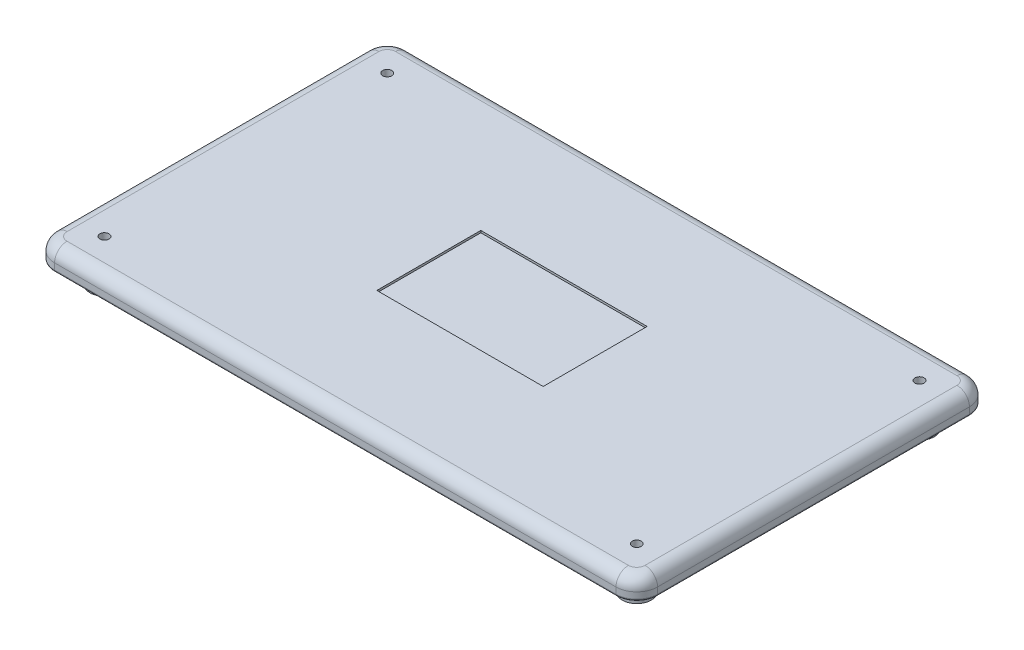
SolidWorks part; units mm, degrees
ref_plane "Front Plane" through (0, 0, 0) normal (0, 0, 1) x (1, 0, 0)
ref_plane "Top Plane" through (0, 0, 0) normal (0, 1, 0) x (1, 0, 0)
ref_plane "Right Plane" through (0, 0, 0) normal (1, 0, 0) x (0, 0, -1)
sketch "Sketch1" plane through (0, 0, 0) normal (0, 1, 0) x (1, 0, 0)
  line L1 (-72.5, 42.5) -> (72.5, 42.5)
  line L2 (-72.5, 42.5) -> (-72.5, -42.5)
  line L3 (-72.5, -42.5) -> (72.5, -42.5)
  line L4 (72.5, 42.5) -> (72.5, -42.5)
  line L5 (-72.5, 42.5) -> (72.5, -42.5) construction
  line L6 (-72.5, -42.5) -> (72.5, 42.5) construction
  point P0 (0, 0)
  dimension "D1" = 145
  dimension "D2" = 85
extrude "Boss-Extrude1" add sketch "Sketch1" along normal blind 5
fillet "Fillet1" radius 5 4 edges at (72.5, 2.5, -42.5) (-72.5, 2.5, -42.5) (72.5, 2.5, 42.5) (-72.5, 2.5, 42.5)
fillet "Fillet2" radius 3 8 edges at (71.0355, 5, 41.0355) (0, 5, 42.5) (-71.0355, 5, 41.0355) (-72.5, 5, 0) (-71.0355, 5, -41.0355) (0, 5, -42.5) (71.0355, 5, -41.0355) (72.5, 5, 0)
shell "Shell1" thickness 2 removed face at (0, 0, 0)
sketch "Sketch3" plane through (0, 3, 0) normal (0, -1, 0) x (1, 0, 0)
  line L0 (-60, -25) -> (-20, -25) construction
  line L1 (-60, 25) -> (60, 25) construction
  line L2 (-60, 25) -> (-60, -25) construction
  line L4 (60, 25) -> (60, -25) construction
  line L5 (-60, 25) -> (60, -25) construction
  line L6 (-60, -25) -> (60, 25) construction
  line L7 (-20, -25) -> (20, -25) construction
  line L8 (20, -25) -> (60, -25) construction
  line L9 (-20, -25) -> (-20, 25) construction
  line L10 (20, -25) -> (20, 25) construction
  circle A0 centre (-60, 25) radius 2.5
  circle A1 centre (-60, -25) radius 2.5
  circle A2 centre (60, -25) radius 2.5
  circle A3 centre (60, 25) radius 2.5
  circle A4 centre (-20, -25) radius 2.5
  circle A5 centre (20, -25) radius 2.5
  circle A6 centre (20, 25) radius 2.5
  circle A7 centre (-20, 25) radius 2.5
  point P0 (0, 0)
  dimension "D3" = 5
  dimension "D1" = 50
  dimension "D2" = 120
extrude "Boss-Extrude2" add sketch "Sketch3" along normal blind 5
sketch "Sketch2" plane through (0, 5, 0) normal (0, -1, 0) x (1, 0, 0)
  line L1 (-20, 12.5) -> (20, 12.5)
  line L2 (-20, 12.5) -> (-20, -12.5)
  line L3 (-20, -12.5) -> (20, -12.5)
  line L4 (20, 12.5) -> (20, -12.5)
  line L5 (-20, 12.5) -> (20, -12.5) construction
  line L6 (-20, -12.5) -> (20, 12.5) construction
  point P0 (0, 0)
  dimension "D1" = 25
  dimension "D2" = 40
extrude "Cut-Extrude1" cut sketch "Sketch2" along normal blind 0.5
sketch "Sketch4" plane through (0, -2, 0) normal (0, -1, 0) x (1, 0, 0)
  line L1 (-64, 34) -> (64, 34) construction
  line L2 (-64, 34) -> (-64, -34) construction
  line L3 (-64, -34) -> (64, -34) construction
  line L4 (64, 34) -> (64, -34) construction
  line L5 (-64, 34) -> (64, -34) construction
  line L6 (-64, -34) -> (64, 34) construction
  circle A1 centre (-64, 34) radius 3.5
  circle A2 centre (-64, -34) radius 3.5
  circle A3 centre (64, 34) radius 3.5
  circle A4 centre (64, -34) radius 3.5
  point P2 (0, 0)
  dimension "D1" = 7
  dimension "D2" = 128
  dimension "D3" = 68
extrude "Boss-Extrude3" add sketch "Sketch4" along normal blind 3 and the other way up to body separate body
hole_wizard "Ø2.2 (2.2) Diameter Hole1" positions "Sketch6" profile "Sketch7" hole size "Ø2.2" standard "ANSI Metric"
sketch "Sketch6" plane through (0, -2, 0) normal (0, -1, 0) x (-1, 0, 0)
  point P0 (-60, -25)
  point P3 (-60, 25)
  point P6 (-20, 25)
  point P9 (-20, -25)
  point P12 (20, -25)
  point P15 (20, 25)
  point P18 (60, 25)
  point P21 (60, -25)
sketch "Sketch7" plane through (60, -2, 25) normal (1, 0, 0) x (0, 0, -1)
  line L0 (0, 0) -> (0, 5)
  line L1 (0, 5) -> (1.1, 4.3391)
  line L2 (1.1, 4.3391) -> (1.1, 0)
  line L5 (1.1, 0) -> (0, 0)
  line L10 (0, 5) -> (-1.1, 4.3391) construction
  line L11 (0, -6.35) -> (0, 107.95) construction
  dimension "Hole Dia." = 2.2
  dimension "Hole Depth" = 5
  dimension "Drill Angle" = 118
hole_wizard "Ø2.2 (2.2) Diameter Hole2" positions "Sketch8" profile "Sketch9" hole size "Ø2.2" standard "ANSI Metric" end condition through all
sketch "Sketch8" plane through (0, -5, 0) normal (0, -1, 0) x (-1, 0, 0)
  point P0 (-64, -34)
  point P3 (-64, 34)
  point P6 (64, 34)
  point P9 (64, -34)
sketch "Sketch9" plane through (64, -5, 34) normal (1, 0, 0) x (0, 0, -1)
  line L0 (0, 0) -> (0, 10)
  line L1 (0, 10) -> (1.1, 10)
  line L2 (1.1, 10) -> (1.1, 0)
  line L5 (1.1, 0) -> (0, 0)
  line L11 (0, -6.35) -> (0, 107.95) construction
  dimension "Thru Hole Dia." = 2.2
  dimension "Thru Hole Depth" = 10
fillet "Fillet3" radius 0.5 8 edges at (71.0355, 0, -41.0355) (72.5, 0, 0) (71.0355, 0, 41.0355) (0, 0, 42.5) (-71.0355, 0, 41.0355) (-72.5, 0, 0) (-71.0355, 0, -41.0355) (0, 0, -42.5)
sketch "Sketch10" plane through (0, 0, 0) normal (0, -1, 0) x (1, 0, 0)
  line L4 (70.5, 37.5) -> (70.5, -37.5) construction
  line L5 (67.5, -40.5) -> (-67.5, -40.5) construction
  line L6 (-70.5, -37.5) -> (-70.5, 37.5) construction
  line L7 (-67.5, 40.5) -> (67.5, 40.5) construction
  line L8 (-67.5, -40.7) -> (67.5, -40.7)
  line L9 (70.7, -37.5) -> (70.7, 37.5)
  line L10 (67.5, 40.7) -> (-67.5, 40.7)
  line L11 (-70.7, 37.5) -> (-70.7, -37.5)
  line L12 (-67.5, -40.7) -> (67.5, -40.7)
  line L13 (70.7, -37.5) -> (70.7, 37.5)
  line L14 (67.5, 40.7) -> (-67.5, 40.7)
  line L15 (-70.7, 37.5) -> (-70.7, -37.5)
  line L16 (70.5, 37.5) -> (70.5, -37.5)
  line L17 (67.5, -40.5) -> (-67.5, -40.5)
  line L18 (-70.5, -37.5) -> (-70.5, 37.5)
  line L19 (-67.5, 40.5) -> (67.5, 40.5)
  arc A4 (67.5, -40.5) -> (70.5, -37.5) centre (67.5, -37.5) ccw construction
  arc A5 (-70.5, -37.5) -> (-67.5, -40.5) centre (-67.5, -37.5) ccw construction
  arc A6 (-67.5, 40.5) -> (-70.5, 37.5) centre (-67.5, 37.5) ccw construction
  arc A7 (70.5, 37.5) -> (67.5, 40.5) centre (67.5, 37.5) ccw construction
  arc A8 (67.5, -40.7) -> (70.7, -37.5) centre (67.5, -37.5) ccw
  arc A9 (70.7, 37.5) -> (67.5, 40.7) centre (67.5, 37.5) ccw
  arc A10 (-67.5, 40.7) -> (-70.7, 37.5) centre (-67.5, 37.5) ccw
  arc A11 (-70.7, -37.5) -> (-67.5, -40.7) centre (-67.5, -37.5) ccw
  arc A12 (67.5, -40.7) -> (70.7, -37.5) centre (67.5, -37.5) ccw
  arc A13 (70.7, 37.5) -> (67.5, 40.7) centre (67.5, 37.5) ccw
  arc A14 (-67.5, 40.7) -> (-70.7, 37.5) centre (-67.5, 37.5) ccw
  arc A15 (-70.7, -37.5) -> (-67.5, -40.7) centre (-67.5, -37.5) ccw
  arc A16 (67.5, -40.5) -> (70.5, -37.5) centre (67.5, -37.5) ccw
  arc A17 (-70.5, -37.5) -> (-67.5, -40.5) centre (-67.5, -37.5) ccw
  arc A18 (-67.5, 40.5) -> (-70.5, 37.5) centre (-67.5, 37.5) ccw
  arc A19 (70.5, 37.5) -> (67.5, 40.5) centre (67.5, 37.5) ccw
  dimension "D1" = 1.3
extrude "Cut-Extrude2" cut sketch "Sketch10" against normal blind 2
